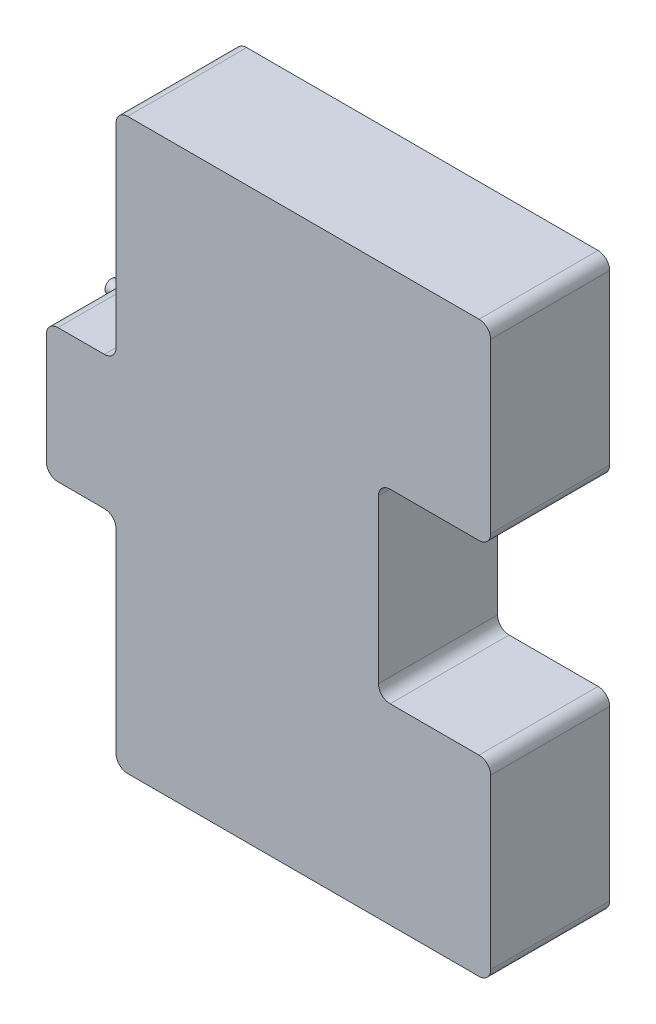
SolidWorks part; units mm, degrees
ref_plane "Front Plane" through (0, 0, 0) normal (0, 0, 1) x (1, 0, 0)
ref_plane "Top Plane" through (0, 0, 0) normal (0, 1, 0) x (1, 0, 0)
ref_plane "Right Plane" through (0, 0, 0) normal (1, 0, 0) x (0, 0, -1)
sketch "Sketch1" plane through (0, 0, 0) normal (0, 0, 1) x (1, 0, 0)
  line L1 (-335.812, 398.7517) -> (309.188, 398.7517)
  line L2 (-455.812, 23.7517) -> (-455.812, -206.2483)
  line L3 (-335.812, -581.2483) -> (309.188, -581.2483)
  line L4 (309.188, 398.7517) -> (309.188, 68.7517)
  line L5 (-335.812, 398.7517) -> (-335.812, 23.7517)
  line L6 (-335.812, 23.7517) -> (-455.812, 23.7517)
  line L7 (309.188, 68.7517) -> (116.0246, 68.7517)
  line L8 (-455.812, -206.2483) -> (-335.812, -206.2483)
  line L9 (-335.812, -206.2483) -> (-335.812, -581.2483)
  line L10 (116.0246, 68.7517) -> (116.0246, -251.2483)
  line L11 (116.0246, -251.2483) -> (309.188, -251.2483)
  line L12 (309.188, -251.2483) -> (309.188, -581.2483)
  dimension "D1" = 320
  dimension "D2" = 330
  dimension "D3" = 330
  dimension "D4" = 375
  dimension "D5" = 375
  dimension "D6" = 120
  dimension "D7" = 120
  dimension "D8" = 645
  dimension "D9" = 645
extrude "Boss-Extrude1" add sketch "Sketch1" along normal blind 10
fillet "Fillet1" radius 20 12 edges at (309.188, 398.7517, 5) (309.188, 68.7517, 5) (116.0246, 68.7517, 5) (309.188, -251.2483, 5) (116.0246, -251.2483, 5) (309.188, -581.2483, 5) (-335.812, -581.2483, 5) (-335.812, -206.2483, 5) (-335.812, 23.7517, 5) (-335.812, 398.7517, 5) (-455.812, 23.7517, 5) (-455.812, -206.2483, 5)
sketch "Sketch2" plane through (0, 0, 10) normal (0, 0, 1) x (1, 0, 0)
  line L24 (299.188, 88.7517) -> (299.188, 378.7517)
  line L25 (289.188, 388.7517) -> (-315.812, 388.7517)
  line L26 (-325.812, 378.7517) -> (-325.812, 43.7517)
  line L27 (-355.812, 13.7517) -> (-435.812, 13.7517)
  line L28 (-445.812, 3.7517) -> (-445.812, -186.2483)
  line L29 (-435.812, -196.2483) -> (-355.812, -196.2483)
  line L30 (-325.812, -226.2483) -> (-325.812, -561.2483)
  line L31 (-315.812, -571.2483) -> (289.188, -571.2483)
  line L32 (299.188, -561.2483) -> (299.188, -271.2483)
  line L33 (289.188, -261.2483) -> (136.0246, -261.2483)
  line L34 (106.0246, -231.2483) -> (106.0246, 48.7517)
  line L35 (136.0246, 78.7517) -> (289.188, 78.7517)
  line L36 (299.188, 88.7517) -> (299.188, 378.7517)
  line L37 (289.188, 388.7517) -> (-315.812, 388.7517)
  line L38 (-325.812, 378.7517) -> (-325.812, 43.7517)
  line L39 (-355.812, 13.7517) -> (-435.812, 13.7517)
  line L40 (-445.812, 3.7517) -> (-445.812, -186.2483)
  line L41 (-435.812, -196.2483) -> (-355.812, -196.2483)
  line L42 (-325.812, -226.2483) -> (-325.812, -561.2483)
  line L43 (-315.812, -571.2483) -> (289.188, -571.2483)
  line L44 (299.188, -561.2483) -> (299.188, -271.2483)
  line L45 (289.188, -261.2483) -> (136.0246, -261.2483)
  line L46 (106.0246, -231.2483) -> (106.0246, 48.7517)
  line L47 (136.0246, 78.7517) -> (289.188, 78.7517)
  line L48 (309.188, 88.7517) -> (309.188, 378.7517)
  line L49 (289.188, 398.7517) -> (-315.812, 398.7517)
  line L50 (-335.812, 378.7517) -> (-335.812, 43.7517)
  line L51 (-355.812, 23.7517) -> (-435.812, 23.7517)
  line L52 (-455.812, 3.7517) -> (-455.812, -186.2483)
  line L53 (-435.812, -206.2483) -> (-355.812, -206.2483)
  line L54 (-335.812, -226.2483) -> (-335.812, -561.2483)
  line L55 (-315.812, -581.2483) -> (289.188, -581.2483)
  line L56 (309.188, -561.2483) -> (309.188, -271.2483)
  line L57 (289.188, -251.2483) -> (136.0246, -251.2483)
  line L58 (116.0246, -231.2483) -> (116.0246, 48.7517)
  line L59 (136.0246, 68.7517) -> (289.188, 68.7517)
  line L60 (309.188, 88.7517) -> (309.188, 378.7517)
  line L61 (289.188, 398.7517) -> (-315.812, 398.7517)
  line L62 (-335.812, 378.7517) -> (-335.812, 43.7517)
  line L63 (-355.812, 23.7517) -> (-435.812, 23.7517)
  line L64 (-455.812, 3.7517) -> (-455.812, -186.2483)
  line L65 (-435.812, -206.2483) -> (-355.812, -206.2483)
  line L66 (-335.812, -226.2483) -> (-335.812, -561.2483)
  line L67 (-315.812, -581.2483) -> (289.188, -581.2483)
  line L68 (309.188, -561.2483) -> (309.188, -271.2483)
  line L69 (289.188, -251.2483) -> (136.0246, -251.2483)
  line L70 (116.0246, -231.2483) -> (116.0246, 48.7517)
  line L71 (136.0246, 68.7517) -> (289.188, 68.7517)
  arc A24 (299.188, 378.7517) -> (289.188, 388.7517) centre (289.188, 378.7517) ccw
  arc A25 (-315.812, 388.7517) -> (-325.812, 378.7517) centre (-315.812, 378.7517) ccw
  arc A26 (-355.812, 13.7517) -> (-325.812, 43.7517) centre (-355.812, 43.7517) ccw
  arc A27 (-435.812, 13.7517) -> (-445.812, 3.7517) centre (-435.812, 3.7517) ccw
  arc A28 (-445.812, -186.2483) -> (-435.812, -196.2483) centre (-435.812, -186.2483) ccw
  arc A29 (-325.812, -226.2483) -> (-355.812, -196.2483) centre (-355.812, -226.2483) ccw
  arc A30 (-325.812, -561.2483) -> (-315.812, -571.2483) centre (-315.812, -561.2483) ccw
  arc A31 (289.188, -571.2483) -> (299.188, -561.2483) centre (289.188, -561.2483) ccw
  arc A32 (299.188, -271.2483) -> (289.188, -261.2483) centre (289.188, -271.2483) ccw
  arc A33 (106.0246, -231.2483) -> (136.0246, -261.2483) centre (136.0246, -231.2483) ccw
  arc A34 (136.0246, 78.7517) -> (106.0246, 48.7517) centre (136.0246, 48.7517) ccw
  arc A35 (289.188, 78.7517) -> (299.188, 88.7517) centre (289.188, 88.7517) ccw
  arc A36 (299.188, 378.7517) -> (289.188, 388.7517) centre (289.188, 378.7517) ccw
  arc A37 (-315.812, 388.7517) -> (-325.812, 378.7517) centre (-315.812, 378.7517) ccw
  arc A38 (-355.812, 13.7517) -> (-325.812, 43.7517) centre (-355.812, 43.7517) ccw
  arc A39 (-435.812, 13.7517) -> (-445.812, 3.7517) centre (-435.812, 3.7517) ccw
  arc A40 (-445.812, -186.2483) -> (-435.812, -196.2483) centre (-435.812, -186.2483) ccw
  arc A41 (-325.812, -226.2483) -> (-355.812, -196.2483) centre (-355.812, -226.2483) ccw
  arc A42 (-325.812, -561.2483) -> (-315.812, -571.2483) centre (-315.812, -561.2483) ccw
  arc A43 (289.188, -571.2483) -> (299.188, -561.2483) centre (289.188, -561.2483) ccw
  arc A44 (299.188, -271.2483) -> (289.188, -261.2483) centre (289.188, -271.2483) ccw
  arc A45 (106.0246, -231.2483) -> (136.0246, -261.2483) centre (136.0246, -231.2483) ccw
  arc A46 (136.0246, 78.7517) -> (106.0246, 48.7517) centre (136.0246, 48.7517) ccw
  arc A47 (289.188, 78.7517) -> (299.188, 88.7517) centre (289.188, 88.7517) ccw
  arc A48 (309.188, 378.7517) -> (289.188, 398.7517) centre (289.188, 378.7517) ccw
  arc A49 (-315.812, 398.7517) -> (-335.812, 378.7517) centre (-315.812, 378.7517) ccw
  arc A50 (-355.812, 23.7517) -> (-335.812, 43.7517) centre (-355.812, 43.7517) ccw
  arc A51 (-435.812, 23.7517) -> (-455.812, 3.7517) centre (-435.812, 3.7517) ccw
  arc A52 (-455.812, -186.2483) -> (-435.812, -206.2483) centre (-435.812, -186.2483) ccw
  arc A53 (-335.812, -226.2483) -> (-355.812, -206.2483) centre (-355.812, -226.2483) ccw
  arc A54 (-335.812, -561.2483) -> (-315.812, -581.2483) centre (-315.812, -561.2483) ccw
  arc A55 (289.188, -581.2483) -> (309.188, -561.2483) centre (289.188, -561.2483) ccw
  arc A56 (309.188, -271.2483) -> (289.188, -251.2483) centre (289.188, -271.2483) ccw
  arc A57 (116.0246, -231.2483) -> (136.0246, -251.2483) centre (136.0246, -231.2483) ccw
  arc A58 (136.0246, 68.7517) -> (116.0246, 48.7517) centre (136.0246, 48.7517) ccw
  arc A59 (289.188, 68.7517) -> (309.188, 88.7517) centre (289.188, 88.7517) ccw
  arc A60 (309.188, 378.7517) -> (289.188, 398.7517) centre (289.188, 378.7517) ccw
  arc A61 (-315.812, 398.7517) -> (-335.812, 378.7517) centre (-315.812, 378.7517) ccw
  arc A62 (-355.812, 23.7517) -> (-335.812, 43.7517) centre (-355.812, 43.7517) ccw
  arc A63 (-435.812, 23.7517) -> (-455.812, 3.7517) centre (-435.812, 3.7517) ccw
  arc A64 (-455.812, -186.2483) -> (-435.812, -206.2483) centre (-435.812, -186.2483) ccw
  arc A65 (-335.812, -226.2483) -> (-355.812, -206.2483) centre (-355.812, -226.2483) ccw
  arc A66 (-335.812, -561.2483) -> (-315.812, -581.2483) centre (-315.812, -561.2483) ccw
  arc A67 (289.188, -581.2483) -> (309.188, -561.2483) centre (289.188, -561.2483) ccw
  arc A68 (309.188, -271.2483) -> (289.188, -251.2483) centre (289.188, -271.2483) ccw
  arc A69 (116.0246, -231.2483) -> (136.0246, -251.2483) centre (136.0246, -231.2483) ccw
  arc A70 (136.0246, 68.7517) -> (116.0246, 48.7517) centre (136.0246, 48.7517) ccw
  arc A71 (289.188, 68.7517) -> (309.188, 88.7517) centre (289.188, 88.7517) ccw
  dimension "D1" = 10
  dimension "D2" = 0
extrude "Boss-Extrude2" add sketch "Sketch2" along normal blind 180
sketch "Sketch3" plane through (0, 0, 190) normal (0, 0, 1) x (1, 0, 0)
  line L12 (309.188, 88.7517) -> (309.188, 378.7517)
  line L13 (289.188, 398.7517) -> (-315.812, 398.7517)
  line L14 (-335.812, 378.7517) -> (-335.812, 43.7517)
  line L15 (-355.812, 23.7517) -> (-435.812, 23.7517)
  line L16 (-455.812, 3.7517) -> (-455.812, -186.2483)
  line L17 (-435.812, -206.2483) -> (-355.812, -206.2483)
  line L18 (-335.812, -226.2483) -> (-335.812, -561.2483)
  line L19 (-315.812, -581.2483) -> (289.188, -581.2483)
  line L20 (309.188, -561.2483) -> (309.188, -271.2483)
  line L21 (289.188, -251.2483) -> (136.0246, -251.2483)
  line L22 (116.0246, -231.2483) -> (116.0246, 48.7517)
  line L23 (136.0246, 68.7517) -> (289.188, 68.7517)
  line L24 (309.188, 88.7517) -> (309.188, 378.7517)
  line L25 (289.188, 398.7517) -> (-315.812, 398.7517)
  line L26 (-335.812, 378.7517) -> (-335.812, 43.7517)
  line L27 (-355.812, 23.7517) -> (-435.812, 23.7517)
  line L28 (-455.812, 3.7517) -> (-455.812, -186.2483)
  line L29 (-435.812, -206.2483) -> (-355.812, -206.2483)
  line L30 (-335.812, -226.2483) -> (-335.812, -561.2483)
  line L31 (-315.812, -581.2483) -> (289.188, -581.2483)
  line L32 (309.188, -561.2483) -> (309.188, -271.2483)
  line L33 (289.188, -251.2483) -> (136.0246, -251.2483)
  line L34 (116.0246, -231.2483) -> (116.0246, 48.7517)
  line L35 (136.0246, 68.7517) -> (289.188, 68.7517)
  arc A12 (289.188, 68.7517) -> (309.188, 88.7517) centre (289.188, 88.7517) ccw
  arc A13 (309.188, 378.7517) -> (289.188, 398.7517) centre (289.188, 378.7517) ccw
  arc A14 (-315.812, 398.7517) -> (-335.812, 378.7517) centre (-315.812, 378.7517) ccw
  arc A15 (-355.812, 23.7517) -> (-335.812, 43.7517) centre (-355.812, 43.7517) ccw
  arc A16 (-435.812, 23.7517) -> (-455.812, 3.7517) centre (-435.812, 3.7517) ccw
  arc A17 (-455.812, -186.2483) -> (-435.812, -206.2483) centre (-435.812, -186.2483) ccw
  arc A18 (-335.812, -226.2483) -> (-355.812, -206.2483) centre (-355.812, -226.2483) ccw
  arc A19 (-335.812, -561.2483) -> (-315.812, -581.2483) centre (-315.812, -561.2483) ccw
  arc A20 (289.188, -581.2483) -> (309.188, -561.2483) centre (289.188, -561.2483) ccw
  arc A21 (309.188, -271.2483) -> (289.188, -251.2483) centre (289.188, -271.2483) ccw
  arc A22 (116.0246, -231.2483) -> (136.0246, -251.2483) centre (136.0246, -231.2483) ccw
  arc A23 (136.0246, 68.7517) -> (116.0246, 48.7517) centre (136.0246, 48.7517) ccw
  arc A24 (289.188, 68.7517) -> (309.188, 88.7517) centre (289.188, 88.7517) ccw
  arc A25 (309.188, 378.7517) -> (289.188, 398.7517) centre (289.188, 378.7517) ccw
  arc A26 (-315.812, 398.7517) -> (-335.812, 378.7517) centre (-315.812, 378.7517) ccw
  arc A27 (-355.812, 23.7517) -> (-335.812, 43.7517) centre (-355.812, 43.7517) ccw
  arc A28 (-435.812, 23.7517) -> (-455.812, 3.7517) centre (-435.812, 3.7517) ccw
  arc A29 (-455.812, -186.2483) -> (-435.812, -206.2483) centre (-435.812, -186.2483) ccw
  arc A30 (-335.812, -226.2483) -> (-355.812, -206.2483) centre (-355.812, -226.2483) ccw
  arc A31 (-335.812, -561.2483) -> (-315.812, -581.2483) centre (-315.812, -561.2483) ccw
  arc A32 (289.188, -581.2483) -> (309.188, -561.2483) centre (289.188, -561.2483) ccw
  arc A33 (309.188, -271.2483) -> (289.188, -251.2483) centre (289.188, -271.2483) ccw
  arc A34 (116.0246, -231.2483) -> (136.0246, -251.2483) centre (136.0246, -231.2483) ccw
  arc A35 (136.0246, 68.7517) -> (116.0246, 48.7517) centre (136.0246, 48.7517) ccw
  dimension "D1" = 0
extrude "Boss-Extrude3" add sketch "Sketch3" along normal blind 15
sketch "Sketch4" plane through (-455.812, 0, 0) normal (-1, 0, 0) x (0, 0, 1)
  line L0 (40, -32.2447) -> (40, -158.5246) construction
  line L1 (60, -32.2447) -> (60, -158.5246)
  line L2 (20, -32.2447) -> (20, -158.5246)
  line L3 (0, 3.7517) -> (0, -186.2483) construction
  arc A0 (60, -32.2447) -> (20, -32.2447) centre (40, -32.2447) ccw
  arc A1 (20, -158.5246) -> (60, -158.5246) centre (40, -158.5246) ccw
  circle A2 centre (40, -33.0965) radius 11
  circle A3 centre (40, -60.2038) radius 11
  circle A4 centre (40, -87.7157) radius 11
  circle A5 centre (40, -118.8688) radius 11
  circle A6 centre (40, -144.7624) radius 11
  point P2 (40, -95.3847)
  point P17 (77.7556, -95.3847)
  dimension "D1" = 22
  dimension "D2" = 20
  dimension "D3" = 20
extrude "Boss-Extrude4" add sketch "Sketch4" along normal blind 15 contours A0 L2 A1 L1
extrude "Boss-Extrude5" add sketch "Sketch4<3>" along normal blind 38 from surface contours A2 | L0 A3 | L0 A4 | A3 L0 | A4 L0 | A5 L0 | L0 A5 | L0 A6 | A6 L0 region at (-455.812, -144.7624, 44.6685) region at (-455.812, -144.7624, 35.3315) region at (-455.812, -118.8688, 44.6685) region at (-455.812, -118.8688, 35.3315) region at (-455.812, -87.7157, 44.6685) region at (-455.812, -87.7157, 35.3315) region at (-455.812, -60.2038, 44.6685) region at (-455.812, -60.2038, 35.3315) region at (-455.812, -25.5384, 32.4418) starting at face at (-470.812, -95.3847, 40)
sketch "Sketch4<3>" plane through (-455.812, 0, 0) normal (-1, 0, 0) x (0, 0, 1) same geometry as "Sketch4"
